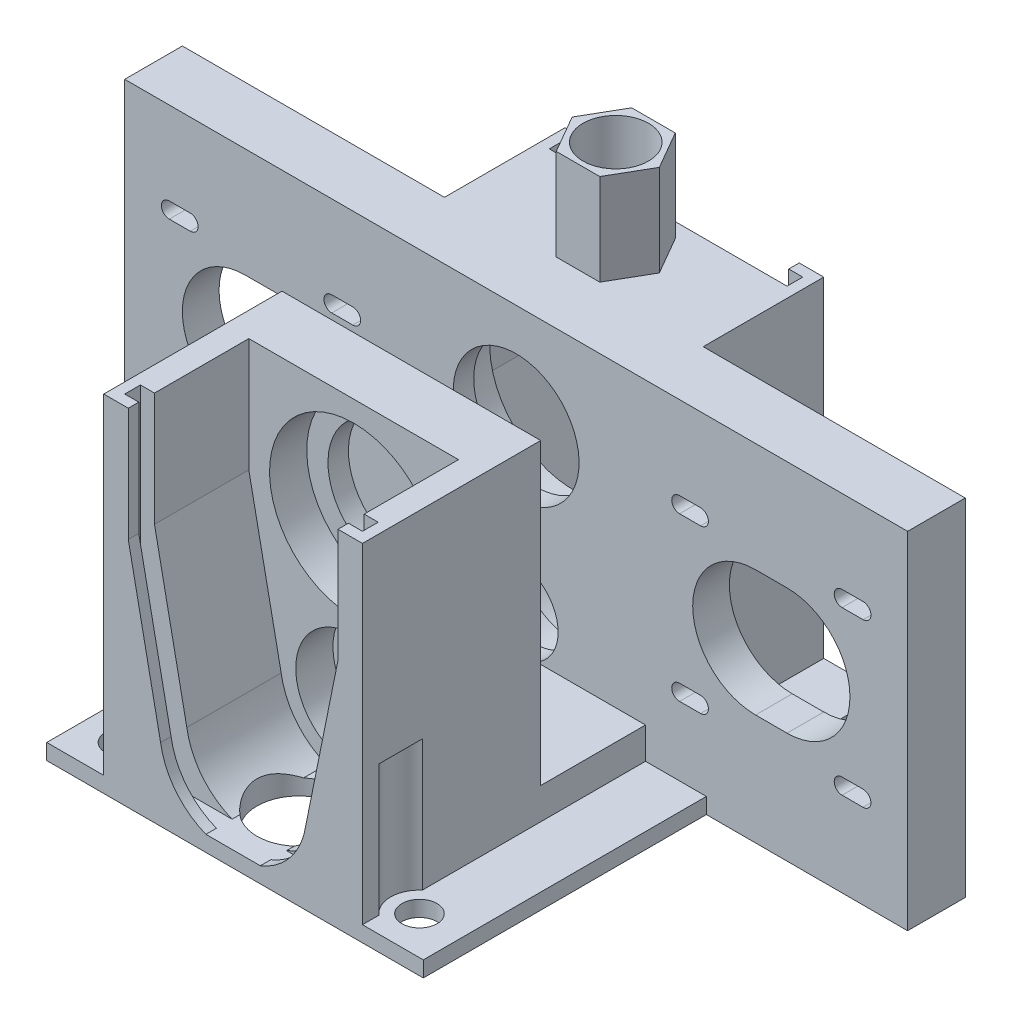
SolidWorks part; units mm, degrees
ref_plane "Front Plane" through (0, 0, 0) normal (0, 0, 1) x (1, 0, 0)
ref_plane "Top Plane" through (0, 0, 0) normal (0, 1, 0) x (1, 0, 0)
ref_plane "Right Plane" through (0, 0, 0) normal (1, 0, 0) x (0, 0, -1)
ref_axis "Axis1" through (88.99, 0, 0) along (-1, 0, 0)
ref_plane "Plane1" through (0, 0, 0) normal (0, 0, -1) x (-1, 0, 0)
ref_plane "Plane2" through (0, 0, 0) normal (0, -1, 0) x (-1, 0, 0)
ref_plane "Plane3" through (0, 0, -42) normal (0, 0, -1) x (-1, 0, 0)
sketch "Sketch2" plane through (0, 0, 0) normal (0, 0, -1) x (-1, 0, 0)
  line L2 (0, 58.0413) -> (0, 28.0413) construction
  line L3 (-24.6785, 78.0413) -> (24.6785, 78.0413)
  line L4 (57.5751, 12.0413) -> (-72.0682, 12.0413) construction
  line L5 (-24.6785, 78.0413) -> (-24.6785, 12.0413)
  line L6 (-24.6785, 12.0413) -> (24.6785, 12.0413)
  line L7 (24.6785, 12.0413) -> (24.6785, 78.0413)
  circle A0 centre (0, 28.0413) radius 11 construction
  circle A1 centre (0, 58.0413) radius 16 construction
  point P4 (0, 58.0413)
  point P6 (0, 28.0413)
  point P7 (20.0824, 64.1811)
  point P8 (15.3009, 32.7193)
  dimension "D1" = 32
  dimension "D2" = 22
  dimension "D6" = 66
  dimension "D3" = 30
  dimension "D5" = 20
  dimension "D4" = 16
extrude "Boss-Extrude1" add sketch "Sketch2" along normal blind 65
ref_plane "Plane5" through (0, 12.0413, 0) normal (0, -1, 0) x (-1, 0, 0)
sketch "Sketch3" plane through (0, 0, 0) normal (0, 0, -1) x (-1, 0, 0)
  line L0 (-24.6785, 12.0413) -> (24.6785, 12.0413) construction
  line L1 (0, 0) -> (0, 102.6324) construction
  circle A0 centre (0, 28.0413) radius 8
  circle A1 centre (0, 58.0413) radius 12
  circle A3 centre (0, 58.0413) radius 16 construction
  circle A4 centre (0, 28.0413) radius 11 construction
  dimension "D1" = 4
  dimension "D2" = 3
  dimension "D4" = 16
  dimension "D5" = 22
  dimension "D6" = 32
  dimension "D3" = 30
extrude "Cut-Extrude1" cut sketch "Sketch3" along normal blind 42
sketch "Sketch5" plane through (0, 0, -42) normal (0, 0, -1) x (-1, 0, 0)
  line L2 (-20, 76.0413) -> (20, 76.0413)
  line L4 (-24.6785, 12.0413) -> (24.6785, 12.0413) construction
  line L6 (13.8042, 25.708) -> (20, 49.5058)
  line L7 (-20, 49.5726) -> (-13.8042, 25.708)
  line L10 (24.6785, 78.0413) -> (-24.6785, 78.0413) construction
  line L11 (-20, 76.0413) -> (-20, 49.5726)
  line L12 (20, 76.0413) -> (20, 49.5058)
  circle A1 centre (0, 58.0413) radius 16 construction
  arc A3 (-13.8042, 25.708) -> (13.8042, 25.708) centre (0, 28.0413) ccw
  dimension "D2" = 16
  dimension "D1" = 14
  dimension "D6" = 32
  dimension "D5" = 2
  dimension "D7" = 30
  dimension "D8" = 20
  dimension "D9" = 20
extrude "Cut-Extrude2" cut sketch "Sketch5" along normal through all
sketch "Sketch6" plane through (0, 0, 0) normal (0, 0, -1) x (-1, 0, 0)
  circle A0 centre (0, 58.0413) radius 16.05
  circle A1 centre (0, 58.0413) radius 12 construction
  circle A2 centre (0, 28.0413) radius 11.05
  circle A3 centre (0, 28.0413) radius 8 construction
  dimension "D1" = 32.1
  dimension "D2" = 22.1
extrude "Cut-Extrude3" cut sketch "Sketch6" along normal blind 7.1
sketch "Sketch7" plane through (0, 0, -42) normal (0, 0, -1) x (-1, 0, 0)
  circle A2 centre (0, 58.0413) radius 16.05
  circle A3 centre (0, 58.0413) radius 16.05
  circle A5 centre (0, 28.0413) radius 11.05
  circle A6 centre (0, 28.0413) radius 11.05
  dimension "D1" = 0
  dimension "D2" = 0
extrude "Cut-Extrude4" cut sketch "Sketch7" against normal blind 7.1
sketch "Sketch8" plane through (0, 0, 0) normal (0, 0, -1) x (-1, 0, 0)
  line L2 (24.6785, 78.0413) -> (-24.6785, 78.0413)
  line L3 (24.6785, 78.0413) -> (24.6785, 12.0413)
  line L4 (24.6785, 12.0413) -> (-24.6785, 12.0413)
  line L5 (-24.6785, 12.0413) -> (-24.6785, 78.0413)
extrude "Boss-Extrude2" add sketch "Sketch8" against normal blind 23
sketch "Sketch9" plane through (0, 0, 0) normal (0, 0, -1) x (-1, 0, 0)
  line L2 (20, 78.0413) -> (-20, 78.0413)
  line L4 (-24.6785, 12.0413) -> (24.6785, 12.0413) construction
  line L5 (20, 78.0413) -> (20, 56.3516)
  line L6 (-20, 56.3516) -> (-13.8326, 25.8825)
  line L7 (13.8326, 25.8825) -> (20, 56.3516)
  line L8 (-20, 78.0413) -> (-20, 56.3516)
  circle A0 centre (0, 56.2822) radius 16 construction
  arc A3 (-13.8326, 25.8825) -> (13.8326, 25.8825) centre (0, 28.0413) ccw
  dimension "D1" = 14
  dimension "D5" = 32
  dimension "D2" = 16
  dimension "D6" = 20
  dimension "D7" = 20
extrude "Cut-Extrude5" cut sketch "Sketch9" against normal through all
ref_plane "Plane4" through (0, 0, -31) normal (0, 0, -1) x (-1, 0, 0)
sketch "Sketch10" plane through (0, 0, -31) normal (0, 0, -1) x (-1, 0, 0)
  line L1 (32.0175, 70.0413) -> (32.0175, 29.2185)
  line L2 (-24.6785, 12.0413) -> (24.6785, 12.0413) construction
  line L5 (-28.9461, 62.8412) -> (-28.9461, 21.0413)
  line L8 (0.9045, 21.0413) -> (-28.9461, 21.0413)
  line L9 (0, 0) -> (0, 85.4363) construction
  line L10 (0.9045, 21.0413) -> (32.0175, 29.2185)
  line L12 (-28.9461, 62.8412) -> (-28.9461, 84.6224)
  line L13 (-28.9461, 84.6224) -> (32.0175, 84.6224)
  line L14 (32.0175, 84.6224) -> (32.0175, 70.0413)
  circle A0 centre (0, 58.0413) radius 10 construction
  circle A1 centre (0, 58.0413) radius 16 construction
  circle A2 centre (0, 28.0413) radius 11 construction
  circle A4 centre (0, 28.0413) radius 4 construction
  dimension "D1" = 32
  dimension "D2" = 22
  dimension "D3" = 30
  dimension "D4" = 20
  dimension "D5" = 8
  dimension "D6" = 16
  dimension "D7" = 7
  dimension "D10" = 7
extrude "Cut-Extrude6" cut sketch "Sketch10" against normal blind 20
sketch "Sketch12" plane through (0, 0, 0) normal (0, 1, 0) x (1, 0, 0)
  circle A0 centre (0, -10.444) radius 8
  ellipse E0 centre (0, -2.444) end of major axis (14, -2.444) minor radius 1.2202 (13.8326, -2.2558) -> (-13.8326, -2.2558) ccw construction
  dimension "D1" = 16
  dimension "D2" = 8
extrude "Cut-Extrude8" cut sketch "Sketch12" along normal up to surface (14.0413 mm away) up to face at (0, 19.9619, 11.5)
sketch "Sketch13" plane through (0, 12.0413, 0) normal (0, -1, 0) x (-1, 0, 0)
  line L2 (24.6785, 11) -> (24.6785, 31)
  line L3 (24.6785, 11) -> (24.6785, 31) construction
  line L4 (24.6785, 31) -> (24.6785, 42)
  line L5 (-24.6785, 65) -> (24.6785, 65) construction
  line L7 (24.6785, 42) -> (74.6785, 42)
  line L8 (97.889, 42) -> (-97.889, 42) construction
  line L9 (74.6785, 42) -> (74.6785, 31)
  line L10 (97.889, 31) -> (-97.889, 31) construction
  line L11 (74.6785, 31) -> (24.6785, 31)
  line L12 (-24.6785, 42) -> (-74.6785, 42)
  line L13 (-24.6785, 65) -> (-24.6785, -23) construction
  line L14 (-74.6785, 42) -> (-74.6785, 31)
  line L15 (-74.6785, 31) -> (-24.6785, 31)
  line L16 (-24.6785, 31) -> (-24.6785, 42)
  dimension "D3" = 50
  dimension "D2" = 23
  dimension "D1" = 0
extrude "Boss-Extrude3" add sketch "Sketch13" against normal up to surface (66 mm away) up to face at (0, 78.0413, -48)
sketch "Sketch15" plane through (0, 0, -42) normal (0, 0, -1) x (-1, 0, 0)
  line L0 (0, 0) -> (0, 87.2744) construction
  line L1 (74.6785, 78.0413) -> (74.6785, 12.0413) construction
  line L2 (25.6785, 66.3413) -> (71.6785, 66.3413)
  line L3 (25.6785, 66.3413) -> (25.6785, 24.0413)
  line L4 (25.6785, 24.0413) -> (71.6785, 24.0413)
  line L5 (71.6785, 66.3413) -> (71.6785, 24.0413)
  line L6 (24.6785, 12.0413) -> (24.6785, 78.0413) construction
  line L7 (-27.1464, 12.0413) -> (27.1464, 12.0413) construction
  line L8 (-71.6785, 66.3413) -> (-71.6785, 24.0413)
  line L9 (-25.6785, 24.0413) -> (-71.6785, 24.0413)
  line L10 (-25.6785, 66.3413) -> (-25.6785, 24.0413)
  line L11 (-25.6785, 66.3413) -> (-71.6785, 66.3413)
  dimension "D1" = 3
  dimension "D2" = 1
  dimension "D3" = 42.3
  dimension "D4" = 12
extrude "Cut-Extrude9" cut sketch "Sketch15" against normal blind 4
sketch "Sketch16" plane through (0, 0, -42) normal (0, 0, -1) x (-1, 0, 0)
  line L0 (-105.1978, 45.1913) -> (88.1587, 45.1913) construction
  line L1 (71.6785, 66.3413) -> (25.6785, 66.3413) construction
  line L2 (25.6785, 24.0413) -> (71.6785, 24.0413) construction
  line L3 (45.6785, 45.1913) -> (51.6785, 45.1913) construction
  line L4 (45.6785, 57.1913) -> (51.6785, 57.1913)
  line L5 (45.6785, 33.1913) -> (51.6785, 33.1913)
  line L6 (48.6785, 83.554) -> (48.6785, 16.5047) construction
  line L7 (25.6785, 66.3413) -> (25.6785, 24.0413) construction
  line L8 (71.6785, 24.0413) -> (71.6785, 66.3413) construction
  line L9 (31.1785, 60.6913) -> (35.1785, 60.6913) construction
  line L10 (31.1785, 62.1913) -> (35.1785, 62.1913)
  line L11 (31.1785, 59.1913) -> (35.1785, 59.1913)
  line L12 (66.1785, 60.6913) -> (62.1785, 60.6913) construction
  line L25 (66.1785, 62.1913) -> (62.1785, 62.1913)
  line L26 (66.1785, 59.1913) -> (62.1785, 59.1913)
  line L27 (31.1785, 29.6913) -> (35.1785, 29.6913) construction
  line L28 (31.1785, 28.1913) -> (35.1785, 28.1913)
  line L29 (31.1785, 31.1913) -> (35.1785, 31.1913)
  line L30 (66.1785, 29.6913) -> (62.1785, 29.6913) construction
  line L31 (66.1785, 28.1913) -> (62.1785, 28.1913)
  line L32 (66.1785, 31.1913) -> (62.1785, 31.1913)
  line L33 (0, 0) -> (0, 89.9864) construction
  line L34 (-45.6785, 45.1913) -> (-51.6785, 45.1913) construction
  line L35 (-45.6785, 57.1913) -> (-51.6785, 57.1913)
  line L36 (-45.6785, 33.1913) -> (-51.6785, 33.1913)
  line L37 (-31.1785, 60.6913) -> (-35.1785, 60.6913) construction
  line L38 (-31.1785, 62.1913) -> (-35.1785, 62.1913)
  line L39 (-31.1785, 59.1913) -> (-35.1785, 59.1913)
  line L40 (-66.1785, 60.6913) -> (-62.1785, 60.6913) construction
  line L41 (-66.1785, 62.1913) -> (-62.1785, 62.1913)
  line L42 (-66.1785, 59.1913) -> (-62.1785, 59.1913)
  line L43 (-31.1785, 29.6913) -> (-35.1785, 29.6913) construction
  line L44 (-31.1785, 28.1913) -> (-35.1785, 28.1913)
  line L45 (-31.1785, 31.1913) -> (-35.1785, 31.1913)
  line L46 (-66.1785, 29.6913) -> (-62.1785, 29.6913) construction
  line L47 (-66.1785, 28.1913) -> (-62.1785, 28.1913)
  line L48 (-66.1785, 31.1913) -> (-62.1785, 31.1913)
  arc A0 (45.6785, 57.1913) -> (45.6785, 33.1913) centre (45.6785, 45.1913) ccw
  arc A1 (51.6785, 33.1913) -> (51.6785, 57.1913) centre (51.6785, 45.1913) ccw
  arc A2 (31.1785, 62.1913) -> (31.1785, 59.1913) centre (31.1785, 60.6913) ccw
  arc A3 (35.1785, 59.1913) -> (35.1785, 62.1913) centre (35.1785, 60.6913) ccw
  arc A16 (66.1785, 62.1913) -> (66.1785, 59.1913) centre (66.1785, 60.6913) cw
  arc A17 (62.1785, 59.1913) -> (62.1785, 62.1913) centre (62.1785, 60.6913) cw
  arc A18 (31.1785, 28.1913) -> (31.1785, 31.1913) centre (31.1785, 29.6913) cw
  arc A19 (35.1785, 31.1913) -> (35.1785, 28.1913) centre (35.1785, 29.6913) cw
  arc A20 (66.1785, 28.1913) -> (66.1785, 31.1913) centre (66.1785, 29.6913) ccw
  arc A21 (62.1785, 31.1913) -> (62.1785, 28.1913) centre (62.1785, 29.6913) ccw
  arc A22 (-45.6785, 57.1913) -> (-45.6785, 33.1913) centre (-45.6785, 45.1913) cw
  arc A23 (-51.6785, 33.1913) -> (-51.6785, 57.1913) centre (-51.6785, 45.1913) cw
  arc A24 (-31.1785, 62.1913) -> (-31.1785, 59.1913) centre (-31.1785, 60.6913) cw
  arc A25 (-35.1785, 59.1913) -> (-35.1785, 62.1913) centre (-35.1785, 60.6913) cw
  arc A26 (-66.1785, 62.1913) -> (-66.1785, 59.1913) centre (-66.1785, 60.6913) ccw
  arc A27 (-62.1785, 59.1913) -> (-62.1785, 62.1913) centre (-62.1785, 60.6913) ccw
  arc A28 (-31.1785, 28.1913) -> (-31.1785, 31.1913) centre (-31.1785, 29.6913) ccw
  arc A29 (-35.1785, 31.1913) -> (-35.1785, 28.1913) centre (-35.1785, 29.6913) ccw
  arc A30 (-66.1785, 28.1913) -> (-66.1785, 31.1913) centre (-66.1785, 29.6913) cw
  arc A31 (-62.1785, 31.1913) -> (-62.1785, 28.1913) centre (-62.1785, 29.6913) cw
  point P8 (48.6785, 45.1913)
  point P14 (33.1785, 60.6913)
  point P28 (64.1785, 60.6913)
  point P36 (33.1785, 29.6913)
  point P43 (64.1785, 29.6913)
  point P52 (-48.6785, 45.1913)
  point P59 (-33.1785, 60.6913)
  point P66 (-64.1785, 60.6913)
  point P73 (-33.1785, 29.6913)
  point P80 (-64.1785, 29.6913)
  dimension "D1" = 12
  dimension "D3" = 31
  dimension "D4" = 1.5
  dimension "D2" = 31
  dimension "D5" = 4
  dimension "D6" = 6
extrude "Cut-Extrude10" cut sketch "Sketch16" against normal up to next
sketch "Sketch17" plane through (0, 78.0413, 0) normal (0, 1, 0) x (1, 0, 0)
  line L0 (0, 55.3583) -> (0, 85.749) construction
  line L1 (-35.5458, 50) -> (45.8299, 50) construction
  line L4 (97.889, 42) -> (-97.889, 42) construction
  line L5 (8.3138, 50) -> (4.1569, 57.2)
  line L6 (4.1569, 57.2) -> (-4.1569, 57.2)
  line L7 (-4.1569, 57.2) -> (-8.3138, 50)
  line L8 (-8.3138, 50) -> (-4.1569, 42.8)
  line L9 (-4.1569, 42.8) -> (4.1569, 42.8)
  line L10 (4.1569, 42.8) -> (8.3138, 50)
  circle A0 centre (0, 50) radius 7.2 construction
  circle A1 centre (0, 50) radius 6.25
  dimension "D2" = 12.5
  dimension "D1" = 14.4
  dimension "D3" = 8
extrude "Boss-Extrude4" add sketch "Sketch17" along normal blind 17.45
sketch "Sketch18" plane through (0, 78.0413, 0) normal (0, 1, 0) x (1, 0, 0)
  circle A2 centre (0, 50) radius 6.25
  circle A3 centre (0, 50) radius 6.25
  dimension "D1" = 0
extrude "Cut-Extrude11" cut sketch "Sketch18" against normal up to next
sketch "Sketch19" plane through (0, 12.0413, 0) normal (0, -1, 0) x (-1, 0, 0)
  line L0 (-66.3049, 12.556) -> (66.3049, 12.556) construction
  line L1 (0, 76.6155) -> (0, 65) construction
  line L2 (-61.7241, 74.2802) -> (0.6987, 11.8573) construction
  line L4 (13.4481, 26.0042) -> (0, 12.556) construction
  line L7 (-36.2843, 48.8403) -> (-36.2843, -23)
  line L9 (35.556, 48.8403) -> (35.556, -23)
  line L10 (-36.2843, 48.8403) -> (-36.2843, 65)
  line L12 (35.556, 65) -> (35.556, 48.8403)
  line L27 (0, 42) -> (0, -57.588) construction
  line L28 (-25.9179, -13.3619) -> (-763.264, -750.708) construction
  line L29 (-36.2843, 65) -> (35.556, 65)
  line L30 (-36.2843, -23) -> (35.556, -23)
  circle A3 centre (-28.2843, 40.8403) radius 3.3465
  circle A6 centre (28.2843, 40.8403) radius 3.3465
  circle A7 centre (-28.2843, -15.7282) radius 3.3465
  circle A8 centre (28.2843, -15.7282) radius 3.3465
  circle A10 centre (0, -10.444) radius 8
  circle A11 centre (0, -10.444) radius 8
  point P3 (0, 12.556)
  dimension "D4" = 88
  dimension "D2" = 45
  dimension "D1" = 45
  dimension "D5" = 40
  dimension "D6" = 8
  dimension "D7" = 71.8403
  dimension "D3" = 0
extrude "Boss-Extrude5" add sketch "Sketch19" against normal blind 3
sketch "Sketch20" plane through (0, 15.0413, 0) normal (0, 1, 0) x (1, 0, 0)
  circle A0 centre (-28.2843, -15.7282) radius 5.5
  circle A1 centre (28.2843, -15.7282) radius 5.5
  circle A2 centre (28.2843, 40.8403) radius 5.5
  circle A3 centre (-28.2843, 40.8403) radius 5.5
  dimension "D1" = 11
extrude "Cut-Extrude12" cut sketch "Sketch20" along normal blind 25
sketch "Sketch21" plane through (0, 12.0413, 0) normal (0, -1, 0) x (-1, 0, 0)
  circle A0 centre (-28.2843, 40.8403) radius 3.3465
  arc A1 (-25.1451, 42) -> (-31.4234, 42) centre (-28.2843, 40.8403) ccw construction
  circle A2 centre (28.2843, 40.8403) radius 3.3465
  arc A3 (31.4234, 42) -> (25.1451, 42) centre (28.2843, 40.8403) ccw construction
extrude "Cut-Extrude13" cut sketch "Sketch21" against normal up to next
sketch "Sketch22" plane through (0, 0, 0) normal (1, 0, 0) x (0, 0, -1)
  line L0 (63, 78.0413) -> (63, 15.0413)
  line L3 (65, 78.0413) -> (42, 78.0413) construction
  line L7 (44.9934, 15.0413) -> (65, 15.0413) construction
  line L8 (63, 15.0413) -> (65, 15.0413)
  line L9 (65, 78.0413) -> (65, 15.0413) construction
  line L10 (-21, 81.0679) -> (-21, 15.0413)
  line L12 (-23, 15.0413) -> (-19.8814, 15.0413) construction
  line L13 (-21, 15.0413) -> (-23, 15.0413)
  line L14 (-23, 78.0413) -> (-23, 15.0413) construction
  dimension "D1" = 2
  dimension "D2" = 2
sketch "Sketch23" plane through (0, 78.0413, 0) normal (0, 1, 0) x (1, 0, 0)
  line L0 (-24.6785, 65) -> (24.6785, 65) construction
  line L1 (-22.6785, 63) -> (22.6785, 63)
  line L2 (-22.6785, 63) -> (-22.6785, 60)
  line L3 (-22.6785, 60) -> (22.6785, 60)
  line L4 (22.6785, 63) -> (22.6785, 60)
  line L5 (-24.6785, 65) -> (-24.6785, 44.9934) construction
  line L6 (24.6785, 44.9934) -> (24.6785, 65) construction
  line L8 (-22.6785, -18) -> (22.6785, -18)
  line L9 (-22.6785, -18) -> (-22.6785, -21)
  line L10 (-22.6785, -21) -> (22.6785, -21)
  line L11 (22.6785, -18) -> (22.6785, -21)
  line L12 (-24.6785, 11) -> (-24.6785, -23) construction
  line L13 (24.6785, 11) -> (24.6785, -23) construction
  line L14 (5.1962, -23) -> (-5.1962, -23) construction
  point P20 (22.6785, -19.5)
  dimension "D1" = 2
  dimension "D2" = 2
  dimension "D3" = 2
  dimension "D4" = 3
  dimension "D5" = 2
  dimension "D6" = 3
  dimension "D7" = 2
  dimension "D8" = 2
  dimension "D9" = 45.357
  dimension "D10" = 45.357
extrude "Cut-Extrude14" cut sketch "Sketch23" against normal up to surface (63 mm away) up to face at (-27.9886, 15.0413, 2.5761)
sketch "Sketch24" plane through (0, 0, -65) normal (0, 0, -1) x (-1, 0, 0)
  line L0 (24.6785, 78.0413) -> (-24.6785, 78.0413) construction
  line L1 (-20, 76.0413) -> (20, 76.0413)
  line L2 (-20, 76.0413) -> (-20, 78.0413)
  line L3 (-20, 78.0413) -> (20, 78.0413)
  line L4 (20, 76.0413) -> (20, 78.0413)
extrude "Cut-Extrude15" cut sketch "Sketch24" against normal up to next
